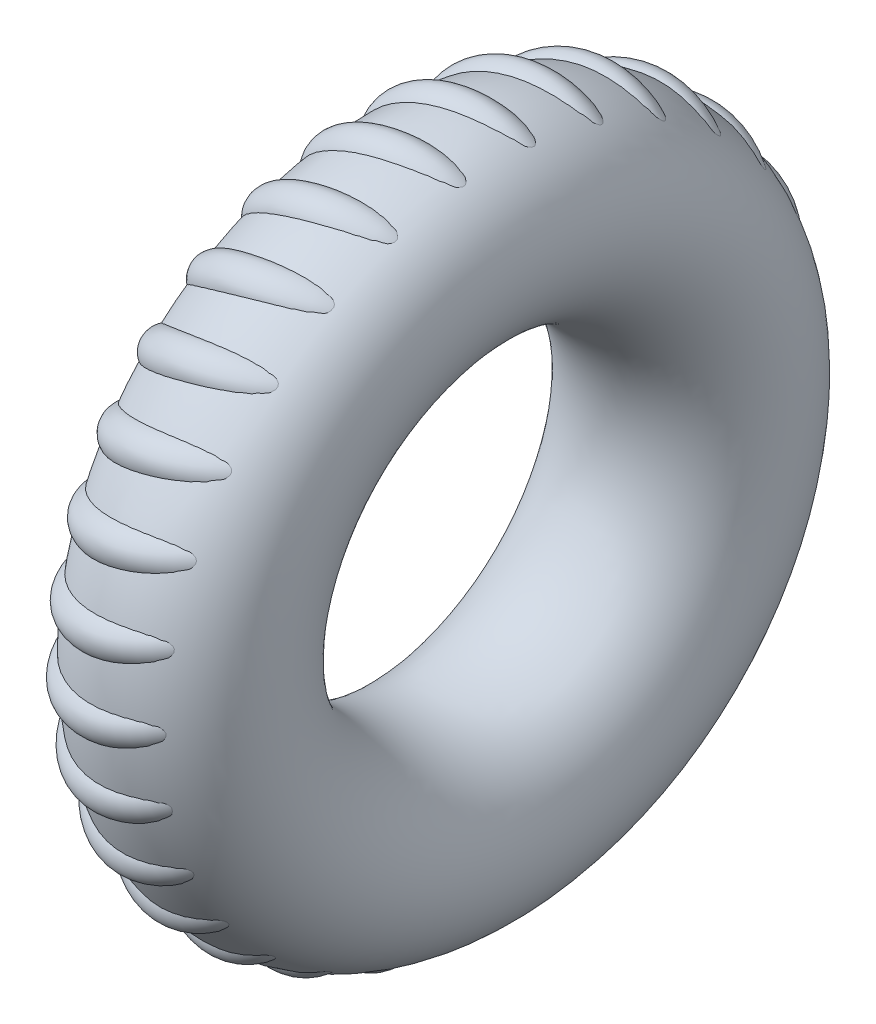
SolidWorks part; units mm, degrees
ref_plane "Front" through (0, 0, 0) normal (0, 0, 1) x (1, 0, 0)
ref_plane "Top" through (0, 0, 0) normal (0, 1, 0) x (1, 0, 0)
ref_plane "Right" through (0, 0, 0) normal (1, 0, 0) x (0, 0, -1)
ref_plane "Plane1" through (0, 0, 0) normal (0, 0, -1) x (-1, 0, 0)
sketch "Sketch1" plane through (0, 0, 0) normal (0, 0, -1) x (-1, 0, 0)
  line L0 (-0.318, 0) -> (0.318, 0) construction
  line L1 (0, 1.2418) -> (0, -1.2418) construction
  ellipse E0 centre (0, 0.8185) end of major axis (-0.2782, 0.9802) minor radius 0.3066
  point P0 (0, 0.8185)
  point P1 (-0.2782, 0.9802)
  point P2 (0.1541, 1.0835)
  dimension "D1" = 0.1241
  dimension "D2" = 0.2782
  dimension "D3" = 0.5535
  dimension "D4" = 0.6567
revolve "Revolve1" add sketch "Sketch1" angle 360 about L0 reverse direction yes
sketch "Sketch2" plane through (0, 0, 0) normal (1, 0, 0) x (0, 0, -1)
  line L0 (0, 1.2215) -> (0.4185, 0.4967)
  line L1 (0, 0.3501) -> (0, -0.3501) construction
  dimension "D1" = 30
  dimension "D2" = 1.2215
ref_plane "Plane2" through (0, 0.3054, -0.5289) normal (0, -0.5, 0.866) x (1, 0, 0)
ref_plane "Plane3" through (0, 0, 0) normal (-1, 0, 0) x (0, 0, 1)
sketch "Sketch5" plane through (0, 0, 0) normal (-1, 0, 0) x (0, 0, 1)
  line L0 (0, 1.2215) -> (-0.4185, 0.4967) construction
  line L1 (-0.2073, 0.8624) -> (-0.5219, 0.907) construction
  circle A0 centre (-0.0807, 1.0818) radius 0.0673
revolve "Revolve3" add sketch "Sketch5" angle 360 about L1
ref_axis "Axis2" through (0, -1.3139, 0) along (0, 1, 0)
move or copy body "Body-Move/Copy1" bodies to move or copy 106 copy no rotation origin (0, 0, 0) rotation axis (0, 1, 0) rotation angle 10
ref_axis "Axis1" through (-0.3503, 0, 0) along (1, 0, 0)
pattern_circular "CirPattern3" count 30 over 360 about axis through (-0.3503, 0, 0) along (1, 0, 0) of bodies 136 106
sketch "Sketch6" plane through (0, 0, 0) normal (1, 0, 0) x (0, 0, -1)
  circle A0 centre (0, 0) radius 0.6858
  dimension "D1" = 1.3716
